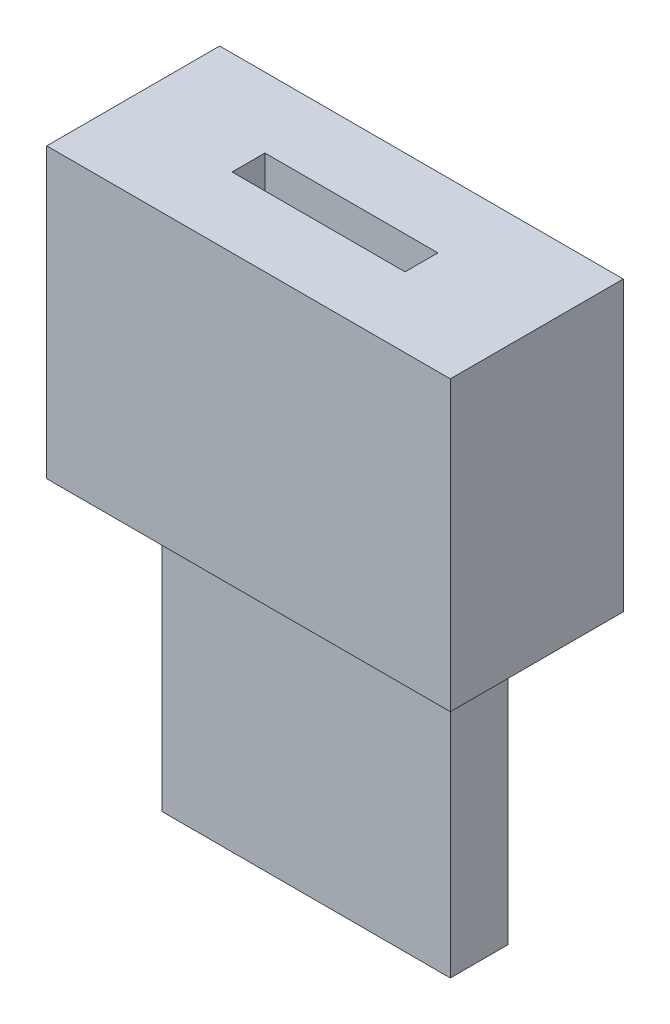
SolidWorks part; units mm, degrees
material "Delrin 2700 NC010, Low Viscosity Acetal Copolymer (SS)"
ref_plane "Front" through (0, 0, 0) normal (0, 0, 1) x (1, 0, 0)
ref_plane "Top" through (0, 0, 0) normal (0, 1, 0) x (1, 0, 0)
ref_plane "Right" through (0, 0, 0) normal (1, 0, 0) x (0, 0, -1)
sketch "Sketch1" plane through (0, 0, 0) normal (0, 1, 0) x (1, 0, 0)
  line L0 (12.5, -2.5) -> (12.5, 2.5)
  line L1 (-17.5, -7.5) -> (17.5, -7.5)
  line L2 (-17.5, -7.5) -> (-17.5, 7.5)
  line L3 (-17.5, 7.5) -> (17.5, 7.5)
  line L4 (17.5, -7.5) -> (17.5, 7.5)
  line L5 (-17.5, -7.5) -> (17.5, 7.5) construction
  line L6 (-17.5, 7.5) -> (17.5, -7.5) construction
  line L7 (-7.5, -1.4246) -> (7.5, -1.4246)
  line L8 (-7.5, -1.4246) -> (-7.5, 1.4246)
  line L9 (-7.5, 1.4246) -> (7.5, 1.4246)
  line L10 (7.5, -1.4246) -> (7.5, 1.4246)
  line L11 (-7.5, -1.4246) -> (7.5, 1.4246) construction
  line L12 (-7.5, 1.4246) -> (7.5, -1.4246) construction
  line L13 (-12.5, 2.5) -> (12.5, 2.5)
  line L14 (-12.5, -2.5) -> (-12.5, 2.5)
  line L15 (-12.5, -2.5) -> (12.5, -2.5)
  point P0 (0, 0)
  point P6 (0, 0)
  point P15 (-13.7388, 9.6538)
  point P16 (0, 0)
  point P17 (7.5, 4.9387)
  point P18 (7.5, 1.4246)
  dimension "D1" = 35
  dimension "D2" = 10
  dimension "D3" = 5
  dimension "D4" = 5
  dimension "D5" = 15
  dimension "D6" = 5
  dimension "D7" = 5
extrude "Boss-Extrude1" add sketch "Sketch1" along normal blind 25 contours L14 L15 L0 L13 L10 L7 L8 L9 | L1 L4 L3 L2 L15 L14 L13 L0 region at (0, 0, 2.245) region at (-17.1192, 0, 0)
extrude "Boss-Extrude2" add sketch "Sketch1<3>" against normal blind 25 contours L14 L15 L0 L13 L10 L7 L8 L9 region at (0, 0, 2.245)
sketch "Sketch1<3>" plane through (0, 0, 0) normal (0, 1, 0) x (1, 0, 0) same geometry as "Sketch1"
